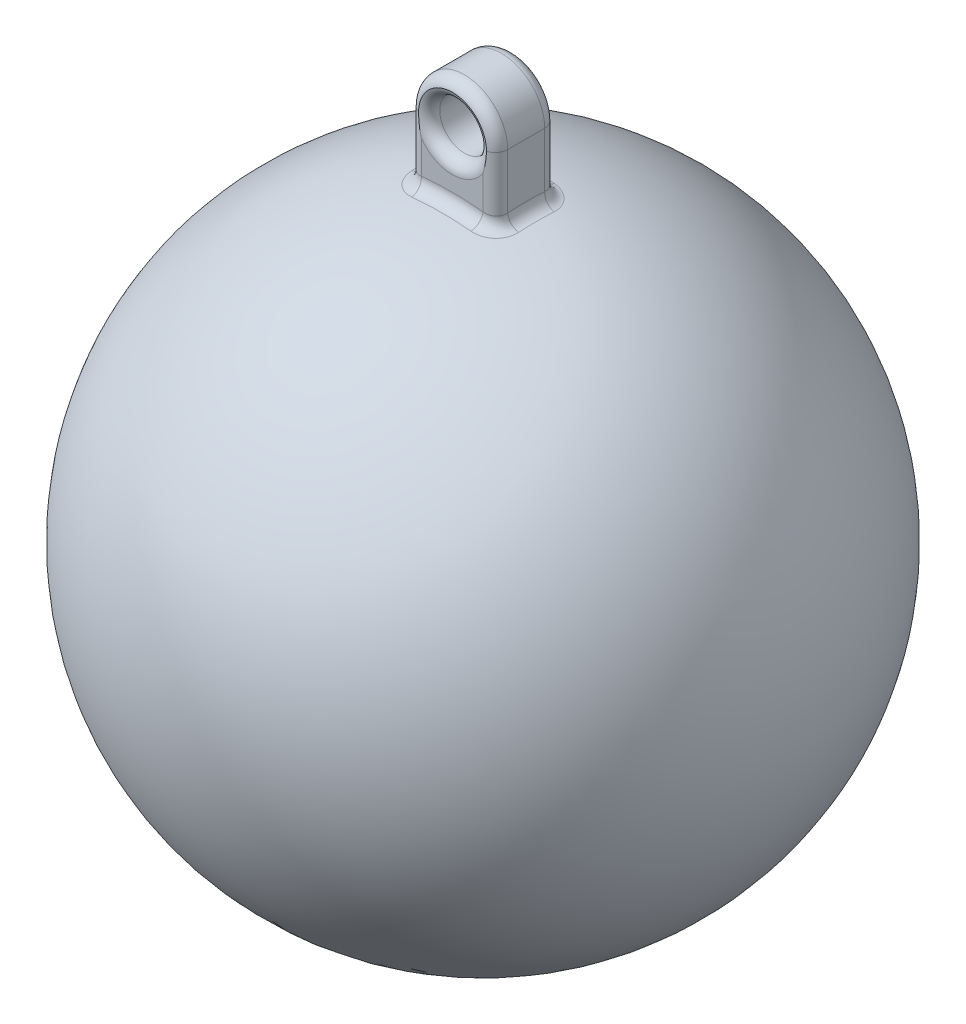
SolidWorks part; units mm, degrees
ref_plane "Front Plane" through (0, 0, 0) normal (0, 0, 1) x (1, 0, 0)
ref_plane "Top Plane" through (0, 0, 0) normal (0, 1, 0) x (1, 0, 0)
ref_plane "Right Plane" through (0, 0, 0) normal (1, 0, 0) x (0, 0, -1)
sketch "Sketch1" plane through (0, 0, 0) normal (0, 1, 0) x (1, 0, 0)
  line L0 (-25, 0) -> (25, 0)
  arc A0 (25, 0) -> (-25, 0) centre (0, 0) ccw
  dimension "D1" = 25
revolve "Revolve1" add sketch "Sketch1" angle 360 about L0
sketch "Sketch2" plane through (0, 0, 0) normal (0, 0, 1) x (1, 0, 0)
  line L0 (0, 0) -> (0, 41.8386) construction
  line L2 (-3.5, 20) -> (3.5, 20)
  line L3 (-3.5, 20) -> (-3.5, 30)
  line L4 (-3.5, 30) -> (3.5, 30) construction
  line L5 (3.5, 20) -> (3.5, 30)
  arc A0 (3.5, 30) -> (-3.5, 30) centre (0, 30) ccw
  circle A1 centre (0, 30) radius 2
  dimension "D1" = 3.5
  dimension "D4" = 4
  dimension "D2" = 20
  dimension "D3" = 10
extrude "Boss-Extrude1" add sketch "Sketch2" along normal mid plane 5
fillet "Fillet1" radius 1 12 edges at (-3.5, 24.7538, 0) (3.5, 24.7538, 0) (2, 30, -2.5) (0, 33.5, -2.5) (-3.5, 27.3136, -2.5) (0, 24.8747, -2.5) (3.5, 27.3136, -2.5) (2, 30, 2.5) (-3.5, 27.3136, 2.5) (0, 33.5, 2.5) (3.5, 27.3136, 2.5) (0, 24.8747, 2.5)
